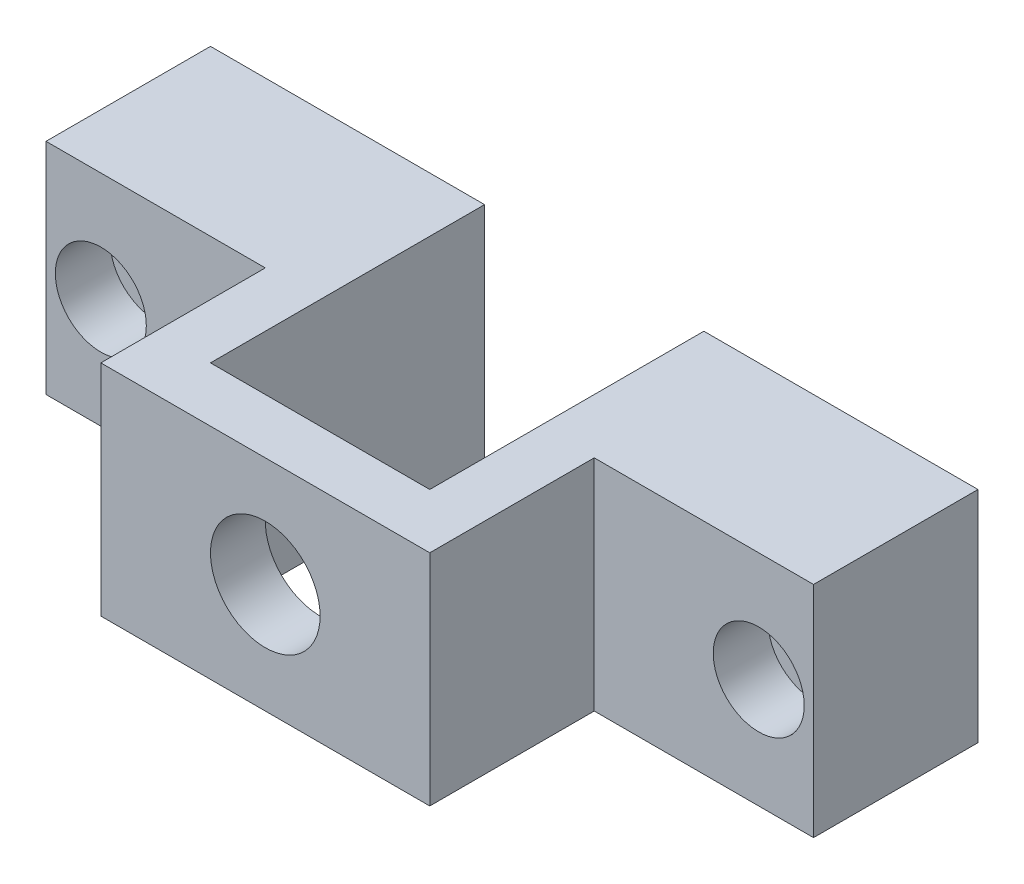
SolidWorks part; units mm, degrees
ref_plane "Front Plane" through (0, 0, 0) normal (0, 0, 1) x (1, 0, 0)
ref_plane "Top Plane" through (0, 0, 0) normal (0, 1, 0) x (1, 0, 0)
ref_plane "Right Plane" through (0, 0, 0) normal (1, 0, 0) x (0, 0, -1)
sketch "Sketch1" plane through (0, 0, 0) normal (0, 0, 1) x (1, 0, 0)
  line L1 (0, 0) -> (70, 0)
  line L2 (0, 0) -> (0, 20)
  line L3 (0, 20) -> (70, 20)
  line L4 (70, 0) -> (70, 20)
  circle A1 centre (65, 10) radius 2.5
  circle A2 centre (5, 10) radius 2.5
  dimension "D1" = 70
  dimension "D2" = 20
extrude "Boss-Extrude1" add sketch "Sketch1" along normal blind 15
sketch "Sketch2" plane through (0, 0, 15) normal (0, 0, 1) x (1, 0, 0)
  line L0 (0, 0) -> (70, 0) construction
  line L1 (20, 0) -> (50, 0)
  line L2 (20, 0) -> (20, 20)
  line L3 (20, 20) -> (50, 20)
  line L4 (50, 0) -> (50, 20)
  line L5 (70, 20) -> (0, 20) construction
extrude "Boss-Extrude2" add sketch "Sketch2" along normal blind 15
sketch "Sketch4" plane through (0, 20, 0) normal (0, 1, 0) x (1, 0, 0)
  line L0 (70, 0) -> (0, 0) construction
  line L1 (25, -25) -> (45, -25)
  line L2 (25, -25) -> (25, 0)
  line L3 (25, 0) -> (45, 0)
  line L4 (45, -25) -> (45, 0)
  dimension "D1" = 25
extrude "Cut-Extrude1" cut sketch "Sketch4" against normal through all
sketch "Sketch5" plane through (0, 0, 30) normal (0, 0, 1) x (1, 0, 0)
  circle A0 centre (35, 10) radius 5
  circle A1 centre (65, 10) radius 2.5 construction
  dimension "D1" = 30
extrude "Cut-Extrude2" cut sketch "Sketch5" against normal through all
sketch "Sketch6" plane through (0, 0, 15) normal (0, 0, 1) x (1, 0, 0)
  circle A0 centre (5, 10) radius 4.15
extrude "Cut-Extrude3" cut sketch "Sketch6" against normal blind 5
sketch "Sketch7" plane through (0, 0, 15) normal (0, 0, 1) x (1, 0, 0)
  circle A0 centre (65, 10) radius 4.15
extrude "Cut-Extrude4" cut sketch "Sketch7" against normal blind 5
